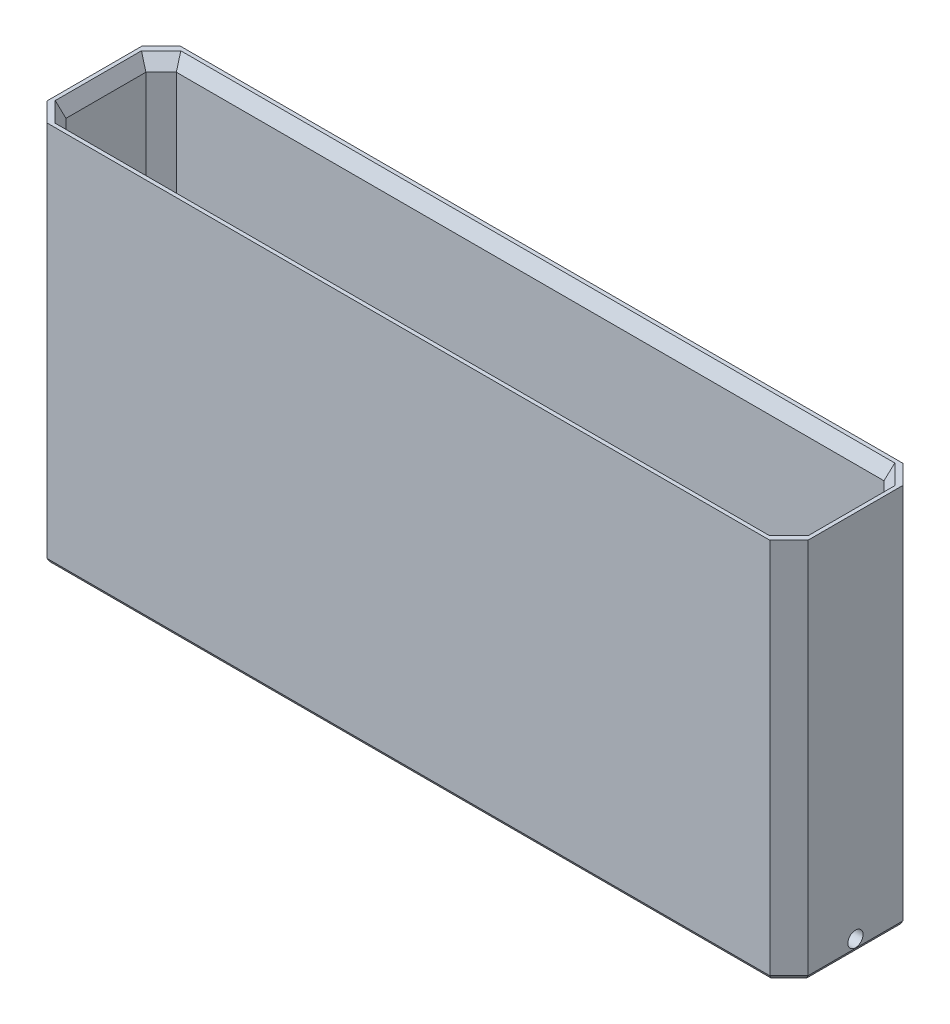
SolidWorks part; units mm, degrees
ref_plane "Front Plane" through (0, 0, 0) normal (0, 0, 1) x (1, 0, 0)
ref_plane "Top Plane" through (0, 0, 0) normal (0, 1, 0) x (1, 0, 0)
ref_plane "Right Plane" through (0, 0, 0) normal (1, 0, 0) x (0, 0, -1)
sketch "Sketch1" plane through (0, 0, 0) normal (0, 1, 0) x (1, 0, 0)
  line L0 (-97, 16.975) -> (-97, 14.5) construction
  line L1 (100, -17.5) -> (-100, -17.5)
  line L2 (100, -17.5) -> (100, 17.5)
  line L3 (100, 17.5) -> (-100, 17.5)
  line L4 (-100, -17.5) -> (-100, 17.5)
  line L5 (100, -17.5) -> (-82.8571, 14.5) construction
  line L6 (100, 17.5) -> (-100, -17.5) construction
  line L7 (-100, 17.5) -> (-97, 17.5)
  line L8 (-100, 17.5) -> (-100, 14.5)
  line L9 (-100, 14.5) -> (-97, 14.5) construction
  line L10 (-97, 17.5) -> (-97, 16.975) construction
  line L11 (97, -14.5) -> (-97, -14.5)
  line L12 (97, -14.5) -> (97, 14.5)
  line L13 (97, 14.5) -> (-97, 14.5)
  line L14 (-97, -14.5) -> (-97, 14.5)
  line L15 (97, -14.5) -> (-97, 14.5) construction
  line L16 (97, 14.5) -> (-97, -14.5) construction
  line L17 (-82.8571, 14.5) -> (-97, 16.975) construction
  line L18 (-97, 16.975) -> (-100, 17.5) construction
  point P0 (0, 0)
  point P9 (0, 0)
extrude "Boss-Extrude1" add sketch "Sketch1" along normal blind 100 contours L4 L1 L2 L3 L11 L14 L13 L12 region at (0, 0, 15.4696)
extrude "Boss-Extrude2" add sketch "Sketch1<3>" along normal blind 3 contours L14 L11 L12 L13 region at (0, 0, 0)
sketch "Sketch1<3>" plane through (0, 0, 0) normal (0, 1, 0) x (1, 0, 0) same geometry as "Sketch1"
chamfer "Chamfer1" distance 4 angle 45 8 edges at (0, 3, -14.5) (97, 51.5, -14.5) (97, 3, 0) (97, 51.5, 14.5) (0, 3, 14.5) (-97, 51.5, 14.5) (-97, 3, 0) (-97, 51.5, -14.5)
chamfer "Chamfer2" distance 5 angle 45 4 edges at (100, 50, -17.5) (100, 50, 17.5) (-100, 50, 17.5) (-100, 50, -17.5)
chamfer "Chamfer3" distance 2 angle 60 8 edges at (95, 100, 12.5) (97, 100, 0) (95, 100, -12.5) (0, 100, 14.5) (-95, 100, 12.5) (-97, 100, 0) (-95, 100, -12.5) (0, 100, -14.5) first distance on face at (0, 100, 0)
sketch "Sketch2" plane through (100, 0, 0) normal (1, 0, 0) x (0, 0, -1)
  line L0 (0, 0) -> (0, 1) construction
  line L1 (-12.5, 0) -> (12.5, 0) construction
  line L2 (0, 1) -> (0, 3) construction
  circle A0 centre (0, 3) radius 2
extrude "Cut-Extrude1" cut sketch "Sketch2" against normal blind 10
mirror "Mirror1" about plane through (0, 0, 0) normal (1, 0, 0) of "Cut-Extrude1"
chamfer "Chamfer4" distance 0.5 angle 60 8 edges at (-97.5, 0, -15) (-100, 0, 0) (-97.5, 0, 15) (0, 0, 17.5) (97.5, 0, 15) (100, 0, 0) (97.5, 0, -15) (0, 0, -17.5) first distance on face at (0, 0, 0)
